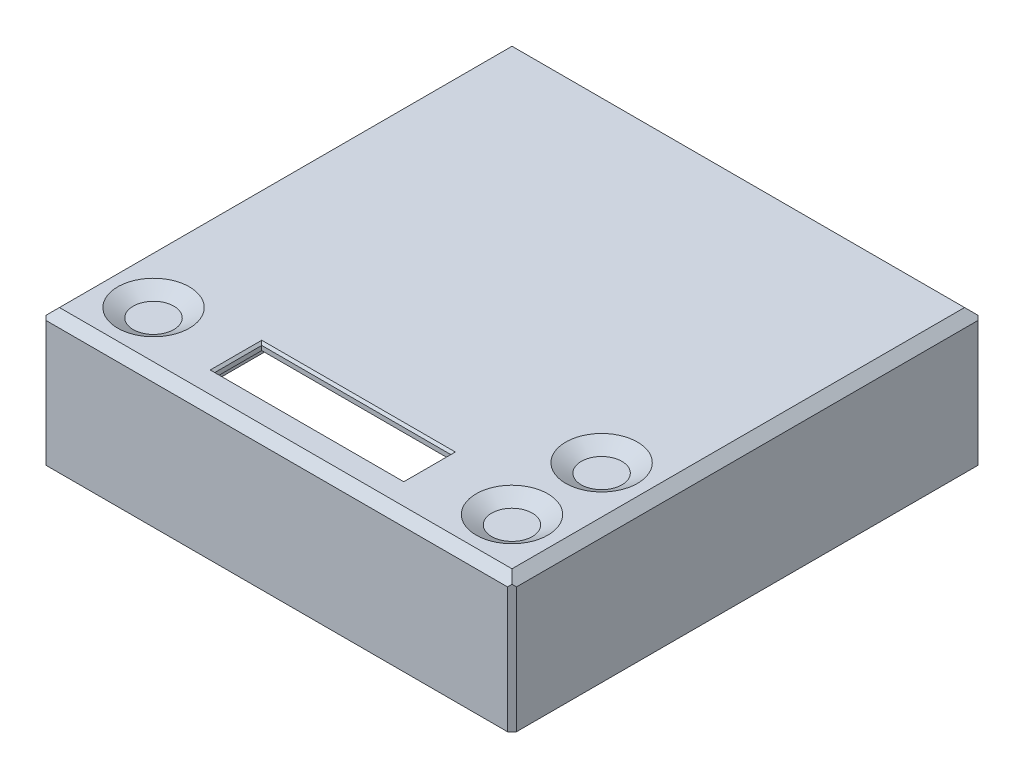
SolidWorks part; units mm, degrees
ref_plane "前视基准面" through (0, 0, 0) normal (0, 0, 1) x (1, 0, 0)
ref_plane "上视基准面" through (0, 0, 0) normal (0, 1, 0) x (1, 0, 0)
ref_plane "右视基准面" through (0, 0, 0) normal (1, 0, 0) x (0, 0, -1)
other "Configuration Table"
sketch "草图1" plane through (0, 0, 0) normal (0, 1, 0) x (1, 0, 0)
  line L0 (-45, 45) -> (45, 45) construction
  line L1 (-50, 50) -> (50, 50)
  line L2 (-50, 50) -> (-50, -50)
  line L3 (-50, -50) -> (50, -50)
  line L4 (50, 50) -> (50, -50)
  line L5 (-50, 50) -> (50, -50) construction
  line L6 (-50, -50) -> (50, 50) construction
  line L7 (-30, -30) -> (30, -30) construction
  line L8 (-40, -40) -> (40, -40) construction
  line L9 (40, -40) -> (40, -20) construction
  line L10 (0, -50) -> (0, -25) construction
  line L11 (28, -31) -> (-24, -31)
  line L12 (28, -31) -> (28, -49)
  line L13 (28, -49) -> (-24, -49)
  line L14 (-24, -31) -> (-24, -49)
  line L15 (0, -25) -> (0, -10) construction
  circle A0 centre (-45, 45) radius 1.75
  circle A1 centre (45, 45) radius 1.75
  circle A2 centre (-30, -30) radius 1.75
  circle A3 centre (30, -30) radius 1.75
  circle A4 centre (-40, -40) radius 5
  circle A5 centre (40, -40) radius 5
  circle A6 centre (40, -20) radius 5
  circle A7 centre (0, -10) radius 2.25
  circle A8 centre (0, -25) radius 2.25
  point P0 (0, 0)
  dimension "D4" = 3.5
  dimension "D8" = 10
  dimension "D13" = 4.5
  dimension "D1" = 100
  dimension "D2" = 100
  dimension "D3" = 5
  dimension "D5" = 20
  dimension "D6" = 10
  dimension "D7" = 20
  dimension "D9" = 52
  dimension "D10" = 18
  dimension "D11" = 1
  dimension "D12" = 22
  dimension "D14" = 25
  dimension "D15" = 15
sketch "草图2" plane through (0, 0, 0) normal (0, 1, 0) x (1, 0, 0)
  line L0 (50, 50) -> (50, -50) construction
  line L1 (-50.5, 50.5) -> (50.5, 50.5)
  line L2 (-50.5, 50.5) -> (-50.5, -50.5)
  line L3 (-50.5, -50.5) -> (50.5, -50.5)
  line L4 (50.5, 50.5) -> (50.5, -50.5)
  line L5 (-50.5, 50.5) -> (50.5, -50.5) construction
  line L6 (-50.5, -50.5) -> (50.5, 50.5) construction
  line L7 (-50, -50) -> (50, -50) construction
  line L9 (-52.5, 52.5) -> (52.5, 52.5)
  line L10 (-52.5, 52.5) -> (-52.5, -52.5)
  line L11 (-52.5, -52.5) -> (52.5, -52.5)
  line L12 (52.5, 52.5) -> (52.5, -52.5)
  line L13 (-52.5, 52.5) -> (52.5, -52.5) construction
  line L14 (-52.5, -52.5) -> (52.5, 52.5) construction
  point P0 (0, 0)
  point P10 (0, 0)
  dimension "D1" = 0.5
  dimension "D2" = 0.5
  dimension "D3" = 2
  dimension "D4" = 2
extrude "凸台-拉伸1" add sketch "草图2" against normal blind 25
extrude "凸台-拉伸2" add sketch "草图2<2>" along normal blind 5 contours L11 L12 L9 L10
sketch "草图2<2>" plane through (0, 0, 0) normal (0, 1, 0) x (1, 0, 0) same geometry as "草图2"
sketch "草图3" plane through (0, 0, 0) normal (0, 1, 0) x (1, 0, 0)
  line L0 (28, -31) -> (28, -49) construction
  line L1 (28, -49) -> (-24, -49) construction
  line L2 (-24, -31) -> (-24, -49) construction
  line L3 (28, -31) -> (-24, -31) construction
  line L4 (28, -31) -> (28, -35)
  line L5 (28, -49) -> (-24, -49)
  line L6 (-24, -31) -> (-24, -49)
  line L7 (28, -31) -> (-24, -31)
  line L8 (28, -35) -> (28, -45) construction
  line L9 (28, -35) -> (30, -35)
  line L10 (28, -35) -> (28, -45) construction
  line L11 (28, -45) -> (30, -45)
  line L12 (30, -35) -> (30, -45)
  line L13 (28, -45) -> (28, -49)
  circle A0 centre (-30, -30) radius 2
  circle A1 centre (-45, 45) radius 2
  circle A2 centre (45, 45) radius 2
  point P17 (-24, -40)
  point P18 (30, -40)
  dimension "D1" = 4
  dimension "D2" = 10
  dimension "D3" = 2
extrude "切除-拉伸1" cut sketch "草图3" along normal blind 3.5
sketch "草图4" plane through (0, 0, 0) normal (0, 1, 0) x (1, 0, 0)
  circle A0 centre (30, -30) radius 1.5
  dimension "D1" = 3
extrude "凸台-拉伸3" add sketch "草图4" against normal blind 3
sketch "草图6" plane through (0, 0, 0) normal (0, 0, 1) x (1, 0, 0)
  line L1 (4.5, -1.5) -> (-4.5, -1.5)
  line L2 (4.5, -1.5) -> (4.5, -5)
  line L3 (4.5, -5) -> (-4.5, -5)
  line L4 (-4.5, -1.5) -> (-4.5, -5)
  line L5 (4.5, -1.5) -> (-4.5, -5) construction
  line L6 (4.5, -5) -> (-4.5, -1.5) construction
  circle A0 centre (-10, -2.25) radius 0.75
  point P0 (0, -3.25)
  dimension "D5" = 1.5
  dimension "D1" = 1.5
  dimension "D2" = 9
  dimension "D3" = 3.5
  dimension "D4" = 10
extrude "切除-拉伸3" cut sketch "草图6" against normal through all
chamfer "倒角3" distance 2 angle 45 4 edges at (0, 5, 52.5) (52.5, 5, 0) (0, 5, -52.5) (-52.5, 5, 0)
chamfer "倒角2" distance 1 angle 45 4 edges at (-52.5, -11, -52.5) (52.5, -11, -52.5) (52.5, -11, 52.5) (-52.5, -11, 52.5)
sketch "草图7" plane through (0, 0, 0) normal (0, 1, 0) x (1, 0, 0)
  circle A0 centre (-40, -40) radius 8
  circle A1 centre (40, -40) radius 8
  circle A2 centre (40, -20) radius 8
  dimension "D1" = 16
extrude "切除-拉伸4" cut sketch "草图7" against normal blind 2 from surface starting at face at (0, 5, 0)
chamfer "倒角4" distance 2 angle 60 3 edges at (40, 3, 48) (40, 3, 28) (-40, 3, 48) first distance on face at (40, 3, 48) first distance on face at (40, 3, 28) first distance on face at (-40, 3, 48)
sketch "草图8" plane through (0, 0, 0) normal (0, 1, 0) x (1, 0, 0)
  line L0 (-40, -40) -> (40, -40) construction
  line L1 (-21.6, -34.25) -> (21.6, -34.25)
  line L2 (-21.6, -34.25) -> (-21.6, -45.75)
  line L3 (-21.6, -45.75) -> (21.6, -45.75)
  line L4 (21.6, -34.25) -> (21.6, -45.75)
  line L5 (-21.6, -34.25) -> (21.6, -45.75) construction
  line L6 (-21.6, -45.75) -> (21.6, -34.25) construction
  point P0 (0, -40)
  dimension "D1" = 43.2
  dimension "D2" = 11.5
extrude "切除-拉伸5" cut sketch "草图8" against normal blind 0.5 from surface starting at face at (-40, 5, 48)
chamfer "倒角5" distance 0.5 angle 45 4 edges at (0, 4.5, 45.75) (21.6, 4.5, 40) (-21.6, 4.5, 40) (0, 4.5, 34.25)
sketch "草图9" plane through (0, 0, 0) normal (0, 1, 0) x (1, 0, 0)
  line L0 (16.1333, -33.3167) -> (16.1333, -26.8167) construction
  line L1 (50.5, 35.4167) -> (35.4167, 35.4167)
  line L2 (50.5, 35.4167) -> (50.5, 39.5)
  line L3 (39.5, 50.5) -> (35.4167, 50.5)
  line L4 (35.4167, 35.4167) -> (35.4167, 50.5)
  line L5 (33.3167, 35.4167) -> (33.3167, 50.5)
  line L6 (33.3167, 35.4167) -> (18.2333, 35.4167)
  line L7 (18.2333, 35.4167) -> (18.2333, 50.5)
  line L8 (33.3167, 50.5) -> (18.2333, 50.5)
  line L9 (16.1333, 35.4167) -> (16.1333, 50.5)
  line L10 (16.1333, 35.4167) -> (1.05, 35.4167)
  line L11 (1.05, 35.4167) -> (1.05, 50.5)
  line L12 (16.1333, 50.5) -> (1.05, 50.5)
  line L13 (-1.05, 35.4167) -> (-1.05, 50.5)
  line L14 (-1.05, 35.4167) -> (-16.1333, 35.4167)
  line L15 (-16.1333, 35.4167) -> (-16.1333, 50.5)
  line L16 (-1.05, 50.5) -> (-16.1333, 50.5)
  line L17 (-18.2333, 35.4167) -> (-18.2333, 50.5)
  line L18 (-18.2333, 35.4167) -> (-33.3167, 35.4167)
  line L19 (-33.3167, 35.4167) -> (-33.3167, 50.5)
  line L20 (-18.2333, 50.5) -> (-33.3167, 50.5)
  line L21 (-35.4167, 35.4167) -> (-35.4167, 50.5)
  line L22 (-35.4167, 35.4167) -> (-50.5, 35.4167)
  line L23 (-50.5, 35.4167) -> (-50.5, 39.5)
  line L24 (-35.4167, 50.5) -> (-39.5, 50.5)
  line L25 (33.3167, 18.2333) -> (33.3167, 33.3167)
  line L26 (33.3167, 18.2333) -> (18.2333, 18.2333)
  line L27 (18.2333, 18.2333) -> (18.2333, 33.3167)
  line L28 (33.3167, 33.3167) -> (18.2333, 33.3167)
  line L29 (16.1333, 18.2333) -> (16.1333, 33.3167)
  line L30 (16.1333, 18.2333) -> (1.05, 18.2333)
  line L31 (1.05, 18.2333) -> (1.05, 33.3167)
  line L32 (16.1333, 33.3167) -> (1.05, 33.3167)
  line L33 (-1.05, 18.2333) -> (-1.05, 33.3167)
  line L34 (-1.05, 18.2333) -> (-16.1333, 18.2333)
  line L35 (-16.1333, 18.2333) -> (-16.1333, 33.3167)
  line L36 (-1.05, 33.3167) -> (-16.1333, 33.3167)
  line L37 (-18.2333, 18.2333) -> (-18.2333, 33.3167)
  line L38 (-18.2333, 18.2333) -> (-33.3167, 18.2333)
  line L39 (-33.3167, 18.2333) -> (-33.3167, 33.3167)
  line L40 (-18.2333, 33.3167) -> (-33.3167, 33.3167)
  line L41 (-35.4167, 18.2333) -> (-35.4167, 33.3167)
  line L42 (-35.4167, 18.2333) -> (-50.5, 18.2333)
  line L43 (-50.5, 18.2333) -> (-50.5, 33.3167)
  line L44 (-35.4167, 33.3167) -> (-50.5, 33.3167)
  line L45 (33.3167, 1.05) -> (33.3167, 16.1333)
  line L46 (33.3167, 1.05) -> (18.2333, 1.05)
  line L47 (18.2333, 1.05) -> (18.2333, 16.1333)
  line L48 (33.3167, 16.1333) -> (18.2333, 16.1333)
  line L49 (16.1333, 1.05) -> (16.1333, 16.1333)
  line L50 (16.1333, 1.05) -> (1.05, 1.05)
  line L51 (1.05, 1.05) -> (1.05, 16.1333)
  line L52 (16.1333, 16.1333) -> (1.05, 16.1333)
  line L53 (-1.05, 1.05) -> (-1.05, 16.1333)
  line L54 (-1.05, 1.05) -> (-16.1333, 1.05)
  line L55 (-16.1333, 1.05) -> (-16.1333, 16.1333)
  line L56 (-1.05, 16.1333) -> (-16.1333, 16.1333)
  line L57 (-18.2333, 1.05) -> (-18.2333, 16.1333)
  line L58 (-18.2333, 1.05) -> (-33.3167, 1.05)
  line L59 (-33.3167, 1.05) -> (-33.3167, 16.1333)
  line L60 (-18.2333, 16.1333) -> (-33.3167, 16.1333)
  line L61 (-35.4167, 1.05) -> (-35.4167, 16.1333)
  line L62 (-35.4167, 1.05) -> (-50.5, 1.05)
  line L63 (-50.5, 1.05) -> (-50.5, 16.1333)
  line L64 (-35.4167, 16.1333) -> (-50.5, 16.1333)
  line L65 (33.3167, -16.1333) -> (33.3167, -1.05)
  line L66 (33.3167, -16.1333) -> (18.2333, -16.1333)
  line L67 (18.2333, -16.1333) -> (18.2333, -1.05)
  line L68 (33.3167, -1.05) -> (18.2333, -1.05)
  line L69 (16.1333, -16.1333) -> (16.1333, -1.05)
  line L70 (16.1333, -16.1333) -> (1.05, -16.1333)
  line L71 (1.05, -16.1333) -> (1.05, -1.05)
  line L72 (16.1333, -1.05) -> (1.05, -1.05)
  line L73 (-1.05, -16.1333) -> (-1.05, -1.05)
  line L74 (-1.05, -16.1333) -> (-16.1333, -16.1333)
  line L75 (-16.1333, -16.1333) -> (-16.1333, -1.05)
  line L76 (-1.05, -1.05) -> (-16.1333, -1.05)
  line L77 (-18.2333, -16.1333) -> (-18.2333, -1.05)
  line L78 (-18.2333, -16.1333) -> (-33.3167, -16.1333)
  line L79 (-33.3167, -16.1333) -> (-33.3167, -1.05)
  line L80 (-18.2333, -1.05) -> (-33.3167, -1.05)
  line L81 (-35.4167, -16.1333) -> (-35.4167, -1.05)
  line L82 (-35.4167, -16.1333) -> (-50.5, -16.1333)
  line L83 (-50.5, -16.1333) -> (-50.5, -1.05)
  line L84 (-35.4167, -1.05) -> (-50.5, -1.05)
  line L85 (33.3167, -33.3167) -> (33.3167, -18.2333) construction
  line L86 (33.3167, -33.3167) -> (18.2333, -33.3167) construction
  line L87 (18.2333, -26.8167) -> (18.2333, -18.2333)
  line L88 (32, -18.2333) -> (18.2333, -18.2333)
  line L89 (16.1333, -26.8167) -> (16.1333, -18.2333)
  line L90 (16.1333, -33.3167) -> (1.05, -33.3167) construction
  line L91 (1.05, -26.8167) -> (1.05, -18.2333)
  line L92 (16.1333, -18.2333) -> (1.05, -18.2333)
  line L93 (-1.05, -26.8167) -> (-1.05, -18.2333)
  line L94 (-1.05, -33.3167) -> (-16.1333, -33.3167) construction
  line L95 (-16.1333, -26.8167) -> (-16.1333, -18.2333)
  line L96 (-1.05, -18.2333) -> (-16.1333, -18.2333)
  line L97 (-18.2333, -26.8167) -> (-18.2333, -18.2333)
  line L98 (-18.2333, -33.3167) -> (-33.3167, -33.3167) construction
  line L99 (-33.3167, -26.8167) -> (-33.3167, -18.2333)
  line L100 (-18.2333, -18.2333) -> (-33.3167, -18.2333)
  line L101 (-35.4167, -32) -> (-35.4167, -18.2333)
  line L102 (-35.4167, -33.3167) -> (-50.5, -33.3167) construction
  line L103 (-50.5, -32) -> (-50.5, -18.2333)
  line L104 (-35.4167, -18.2333) -> (-50.5, -18.2333)
  line L105 (33.3167, -50.5) -> (33.3167, -35.4167) construction
  line L106 (33.3167, -50.5) -> (18.2333, -50.5) construction
  line L107 (18.2333, -50.5) -> (18.2333, -35.4167) construction
  line L108 (33.3167, -35.4167) -> (18.2333, -35.4167) construction
  line L109 (16.1333, -50.5) -> (16.1333, -35.4167) construction
  line L110 (16.1333, -50.5) -> (1.05, -50.5) construction
  line L111 (1.05, -50.5) -> (1.05, -35.4167) construction
  line L112 (16.1333, -35.4167) -> (1.05, -35.4167) construction
  line L113 (-1.05, -50.5) -> (-1.05, -35.4167) construction
  line L114 (-1.05, -50.5) -> (-16.1333, -50.5) construction
  line L115 (-16.1333, -50.5) -> (-16.1333, -35.4167) construction
  line L116 (-1.05, -35.4167) -> (-16.1333, -35.4167) construction
  line L117 (-18.2333, -50.5) -> (-18.2333, -35.4167) construction
  line L118 (-18.2333, -50.5) -> (-33.3167, -50.5) construction
  line L119 (-33.3167, -50.5) -> (-33.3167, -35.4167) construction
  line L120 (-18.2333, -35.4167) -> (-33.3167, -35.4167) construction
  line L121 (-35.4167, -50.5) -> (-35.4167, -35.4167) construction
  line L122 (-35.4167, -50.5) -> (-50.5, -50.5) construction
  line L123 (-50.5, -50.5) -> (-50.5, -35.4167) construction
  line L124 (-35.4167, -35.4167) -> (-50.5, -35.4167) construction
  line L125 (50.5, 18.2333) -> (50.5, 33.3167)
  line L126 (50.5, 18.2333) -> (35.4167, 18.2333)
  line L127 (35.4167, 18.2333) -> (35.4167, 33.3167)
  line L128 (50.5, 33.3167) -> (35.4167, 33.3167)
  line L129 (50.5, 1.05) -> (50.5, 16.1333)
  line L130 (50.5, 1.05) -> (35.4167, 1.05)
  line L131 (35.4167, 1.05) -> (35.4167, 16.1333)
  line L132 (50.5, 16.1333) -> (35.4167, 16.1333)
  line L133 (50.5, -12) -> (50.5, -1.05)
  line L134 (50.5, -16.1333) -> (35.4167, -16.1333) construction
  line L135 (35.4167, -12) -> (35.4167, -1.05)
  line L136 (50.5, -1.05) -> (35.4167, -1.05)
  line L137 (50.5, -33.3167) -> (50.5, -18.2333) construction
  line L138 (50.5, -33.3167) -> (35.4167, -33.3167) construction
  line L139 (35.4167, -33.3167) -> (35.4167, -18.2333) construction
  line L140 (50.5, -18.2333) -> (35.4167, -18.2333) construction
  line L141 (50.5, -50.5) -> (50.5, -35.4167) construction
  line L142 (50.5, -50.5) -> (35.4167, -50.5) construction
  line L143 (35.4167, -50.5) -> (35.4167, -35.4167) construction
  line L144 (50.5, -35.4167) -> (35.4167, -35.4167) construction
  line L145 (-50.5, 50.5) -> (-50.5, -50.5) construction
  line L146 (-50.5, -50.5) -> (50.5, -50.5) construction
  line L147 (50.5, -50.5) -> (50.5, 50.5) construction
  line L148 (32, -26.8167) -> (18.2333, -26.8167)
  line L149 (32, -26.8167) -> (32, -18.2333)
  line L150 (50.5, -12) -> (35.4167, -12)
  line L151 (50.5, -16.1333) -> (50.5, -12) construction
  line L152 (35.4167, -16.1333) -> (35.4167, -12) construction
  line L153 (18.2333, -33.3167) -> (18.2333, -26.8167) construction
  line L154 (18.2333, -26.8167) -> (16.1333, -26.8167) construction
  line L155 (16.1333, -26.8167) -> (1.05, -26.8167)
  line L156 (1.05, -33.3167) -> (1.05, -26.8167) construction
  line L157 (1.05, -26.8167) -> (-1.05, -26.8167) construction
  line L158 (-1.05, -26.8167) -> (-16.1333, -26.8167)
  line L159 (-1.05, -33.3167) -> (-1.05, -26.8167) construction
  line L160 (-16.1333, -33.3167) -> (-16.1333, -26.8167) construction
  line L161 (-16.1333, -26.8167) -> (-18.2333, -26.8167) construction
  line L162 (-18.2333, -26.8167) -> (-33.3167, -26.8167)
  line L163 (-18.2333, -33.3167) -> (-18.2333, -26.8167) construction
  line L164 (-33.3167, -33.3167) -> (-33.3167, -26.8167) construction
  line L165 (-35.4167, -32) -> (-50.5, -32)
  line L166 (-35.4167, -33.3167) -> (-35.4167, -32) construction
  line L167 (-50.5, -33.3167) -> (-50.5, -32) construction
  line L168 (33.3167, -18.2333) -> (32, -18.2333) construction
  line L169 (50.5, 50.5) -> (45, 50.5) construction
  line L170 (50.5, 45) -> (50.5, 50.5) construction
  line L171 (-45, 50.5) -> (-50.5, 50.5) construction
  line L172 (-50.5, 45) -> (-50.5, 50.5) construction
  line L173 (-39.5, 45) -> (-39.5, 50.5)
  line L174 (-45, 39.5) -> (-50.5, 39.5)
  line L175 (39.5, 45) -> (39.5, 50.5)
  line L176 (45, 39.5) -> (50.5, 39.5)
  line L177 (-39.5, 50.5) -> (-45, 50.5) construction
  line L178 (-50.5, 39.5) -> (-50.5, 45) construction
  line L179 (45, 50.5) -> (39.5, 50.5) construction
  line L180 (50.5, 39.5) -> (50.5, 45) construction
  circle A0 centre (-40, -40) radius 8 construction
  arc A1 (39.5, 45) -> (45, 39.5) centre (45, 45) ccw
  circle A2 centre (40, -20) radius 8 construction
  arc A3 (-45, 39.5) -> (-39.5, 45) centre (-45, 45) ccw
  arc A4 (50.5, 45) -> (45, 50.5) centre (45, 45) ccw construction
  arc A5 (-45, 50.5) -> (-50.5, 45) centre (-45, 45) ccw construction
  arc A6 (-39.5, 45) -> (-45, 50.5) centre (-45, 45) ccw construction
  arc A7 (-50.5, 45) -> (-45, 39.5) centre (-45, 45) ccw construction
  arc A8 (45, 50.5) -> (39.5, 45) centre (45, 45) ccw construction
  arc A9 (45, 39.5) -> (50.5, 45) centre (45, 45) ccw construction
  dimension "D1" = 6
  dimension "D2" = 6
  dimension "D3" = 15.0833
  dimension "D4" = 15.0833
  dimension "D5" = 6.5
extrude "切除-拉伸6" cut sketch "草图9" along normal blind 3.5 from surface starting at face at (30, 0, 31.5)
sketch "草图10" plane through (0, 0, 0) normal (0, 1, 0) x (1, 0, 0)
  line L4 (-21.1, -34.75) -> (-21.1, -45.25)
  line L6 (-21.1, -34.75) -> (-21.1, -45.25)
  line L12 (-21.1, -45.25) -> (21.1, -45.25)
  line L14 (-21.1, -45.25) -> (21.1, -45.25)
  line L16 (21.1, -45.25) -> (21.1, -34.75)
  line L17 (21.1, -45.25) -> (21.1, -34.75)
  line L18 (21.1, -34.75) -> (-21.1, -34.75)
  line L19 (21.1, -34.75) -> (-21.1, -34.75)
  dimension "D1" = 0
extrude "切除-拉伸7" cut sketch "草图10" against normal up to next from surface starting at face at (0, 4.5, 40)
sketch "草图11" plane through (0, 0, 0) normal (0, 1, 0) x (1, 0, 0)
  line L0 (-1.05, -1.05) -> (-1.05, -16.1333) construction
  line L1 (1.05, -23.1833) -> (-1.05, -23.1833)
  line L2 (1.05, -23.1833) -> (1.05, -26.8167)
  line L3 (1.05, -26.8167) -> (-1.05, -26.8167)
  line L4 (-1.05, -23.1833) -> (-1.05, -26.8167)
  line L5 (1.05, -23.1833) -> (-1.05, -26.8167) construction
  line L6 (1.05, -26.8167) -> (-1.05, -23.1833) construction
  line L7 (1.05, -8.01) -> (-1.05, -8.01)
  line L8 (1.05, -8.01) -> (1.05, -11.99)
  line L9 (1.05, -11.99) -> (-1.05, -11.99)
  line L10 (-1.05, -8.01) -> (-1.05, -11.99)
  line L11 (1.05, -8.01) -> (-1.05, -11.99) construction
  line L12 (1.05, -11.99) -> (-1.05, -8.01) construction
  circle A0 centre (0, -10) radius 2.25 construction
  point P0 (0, -25)
  point P7 (0, -10)
extrude "切除-拉伸8" cut sketch "草图11" along normal up to surface (3.5 mm away) from surface up to face at (-8.5917, 3.5, 8.5917) starting at face at (30, 0, 31.5)
